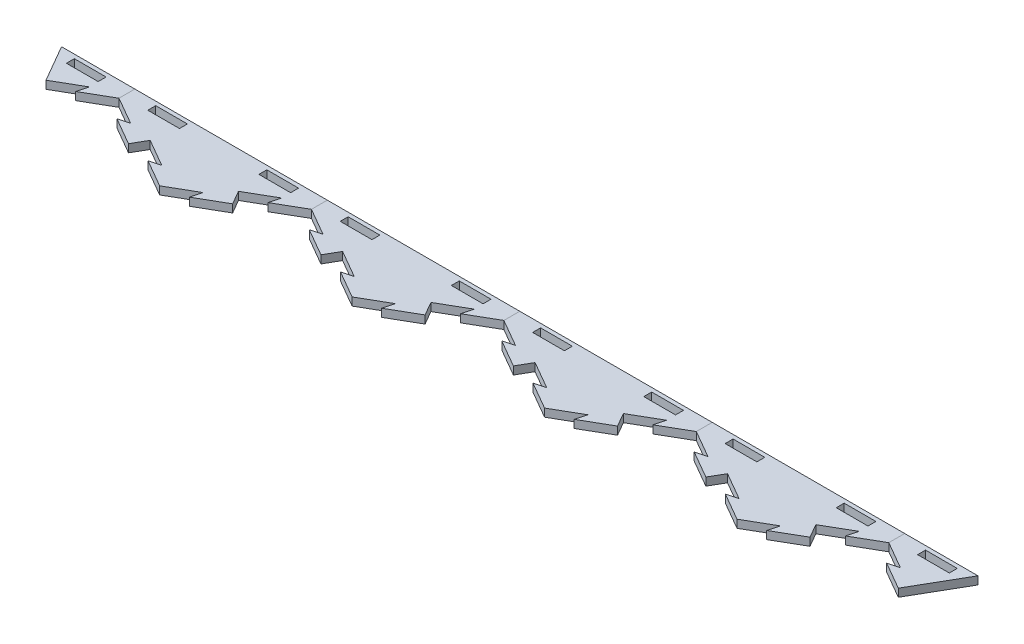
SolidWorks part; units mm, degrees
material "Cedar"
ref_plane "Front Plane" through (0, 0, 0) normal (0, 0, 1) x (1, 0, 0)
ref_plane "Top Plane" through (0, 0, 0) normal (0, 1, 0) x (1, 0, 0)
ref_plane "Right Plane" through (0, 0, 0) normal (1, 0, 0) x (0, 0, -1)
sketch "Sketch1" plane through (0, 0, 0) normal (0, 1, 0) x (1, 0, 0)
  line L0 (-76.9897, 0) -> (76.9897, 0) construction
  line L1 (-76.9897, 0) -> (0, -44.45)
  line L2 (0, -44.45) -> (76.9897, 0)
  line L3 (76.9897, 0) -> (76.9897, 88.9)
  line L4 (76.9897, 88.9) -> (0, 133.35)
  line L5 (0, 133.35) -> (-76.9897, 88.9)
  line L6 (-76.9897, 88.9) -> (-76.9897, 0)
  line L7 (0, -44.45) -> (0, 44.45) construction
  circle A0 centre (0, 44.45) radius 76.9897 construction
  point P1 (17.7378, -55.0895)
  point P9 (0, 0)
  dimension "D1" = 88.9
extrude "Boss-Extrude1" add sketch "Sketch1" against normal blind 6.35
sketch "Sketch2" plane through (0, 0, 0) normal (0, 1, 0) x (1, 0, 0)
  line L0 (-76.9897, 44.45) -> (76.9897, 44.45) construction
  line L1 (-76.9897, 88.9) -> (-76.9897, 0) construction
  line L2 (76.9897, 0) -> (76.9897, 88.9) construction
  point P2 (0, 44.45)
ref_axis "Axis1" through (0, 0, -44.45) along (0, 1, 0)
sketch "Sketch10" plane through (0, 0, 0) normal (0, 1, 0) x (1, 0, 0)
  line L0 (0, -44.45) -> (-21.997, -31.75) construction
  line L1 (-21.997, -31.75) -> (-13.3228, -29.4257)
  line L2 (-13.3228, -29.4257) -> (-35.3198, -16.7257)
  line L3 (-35.3198, -16.7257) -> (-38.4948, -22.225)
  line L4 (-21.997, -31.75) -> (-38.4948, -22.225)
  line L5 (-76.9897, 0) -> (0, -44.45) construction
  dimension "D1" = 45
  dimension "D2" = 6.35
extrude "Cut-Extrude4" cut sketch "Sketch10" against normal through all
sketch "Sketch11" plane through (0, 0, 0) normal (0, 1, 0) x (1, 0, 0)
  line L0 (-38.4948, -22.225) -> (-76.9897, 0) construction
  line L1 (-38.4948, -22.225) -> (-41.6698, -27.7243)
  line L2 (-41.6698, -27.7243) -> (-63.6669, -15.0243)
  line L3 (-63.6669, -15.0243) -> (-54.9926, -12.7)
  line L4 (-54.9926, -12.7) -> (-38.4948, -22.225)
  line L5 (-54.9926, -12.7) -> (-76.9897, 0) construction
  line L6 (-54.9926, -12.7) -> (-76.9897, 0) construction
  line L7 (-76.9897, 0) -> (-38.4948, -22.225) construction
  line L8 (-76.9897, 88.9) -> (-76.9897, 0) construction
  dimension "D1" = 45
  dimension "D2" = 6.35
extrude "Boss-Extrude4" add sketch "Sketch11" against normal blind 6.35
pattern_circular "CirPattern1" count 2 every 60 about axis through (0, 0, -44.45) along (0, 1, 0) of "Cut-Extrude4", "Boss-Extrude4"
sketch "Sketch12" plane through (0, 0, 0) normal (0, 1, 0) x (1, 0, 0)
  line L0 (-76.9897, 12.7) -> (76.9897, 12.7)
  line L1 (-76.9897, 88.9) -> (-76.9897, 0) construction
  line L2 (76.9897, 0) -> (76.9897, 88.9) construction
  line L3 (76.9897, 12.7) -> (76.9897, 133.35)
  line L4 (76.9897, 133.35) -> (-76.9897, 133.35)
  line L5 (-76.9897, 133.35) -> (-76.9897, 12.7)
  line L6 (0, 0) -> (0, 12.7) construction
  dimension "D1" = 12.7
extrude "Cut-Extrude5" cut sketch "Sketch12" against normal through all
sketch "Sketch13" plane through (0, 0, 0) normal (0, 1, 0) x (1, 0, 0)
  line L0 (0, 0) -> (0, 12.7) construction
  line L1 (-76.9897, 12.7) -> (76.9897, 12.7) construction
  line L2 (-44.45, 6.35) -> (44.45, 6.35) construction
  line L4 (-57.15, 9.525) -> (-31.75, 9.525)
  line L5 (-57.15, 9.525) -> (-57.15, 3.175)
  line L6 (-57.15, 3.175) -> (-31.75, 3.175)
  line L7 (-31.75, 9.525) -> (-31.75, 3.175)
  line L8 (-57.15, 9.525) -> (-31.75, 3.175) construction
  line L9 (-57.15, 3.175) -> (-31.75, 9.525) construction
  line L10 (31.75, 9.525) -> (57.15, 9.525)
  line L11 (31.75, 9.525) -> (31.75, 3.175)
  line L12 (31.75, 3.175) -> (57.15, 3.175)
  line L13 (57.15, 9.525) -> (57.15, 3.175)
  line L14 (31.75, 9.525) -> (57.15, 3.175) construction
  line L15 (31.75, 3.175) -> (57.15, 9.525) construction
  point P7 (0, 6.35)
  point P8 (0, 6.35)
  dimension "D1" = 6.35
  dimension "D2" = 25.4
  dimension "D3" = 6.35
  dimension "D4" = 25.4
  dimension "D5" = 88.9
extrude "Cut-Extrude6" cut sketch "Sketch13" against normal through all
pattern_linear "LPattern1" count 5 spacing 153.9793 along (1, 0, 0) count 2 spacing 153.9793 along (-1, 0, 0) pattern seed only yes of bodies 136 131
sketch "Sketch14" plane through (0, 0, 0) normal (0, 1, 0) x (1, 0, 0)
  line L0 (615.9173, -44.45) -> (615.9173, 12.7)
  line L1 (538.9276, 12.7) -> (692.9069, 12.7) construction
  line L2 (615.9173, 12.7) -> (692.9069, 12.7)
  line L3 (692.9069, 12.7) -> (692.9069, -44.45)
  line L4 (692.9069, -44.45) -> (615.9173, -44.45)
  line L5 (-153.9793, -44.45) -> (-153.9793, 12.7)
  line L6 (-230.969, 12.7) -> (-76.9897, 12.7) construction
  line L7 (-153.9793, 12.7) -> (-230.969, 12.7)
  line L8 (-230.969, 12.7) -> (-230.969, -44.45)
  line L9 (-230.969, -44.45) -> (-153.9793, -44.45)
  line L10 (580.5974, -16.7257) -> (597.5864, 12.7)
  line L11 (597.5864, 12.7) -> (615.9173, 12.7)
  line L12 (580.5974, -16.7257) -> (574.2474, -27.7243)
  line L13 (574.2474, -27.7243) -> (615.9173, -44.45)
  line L14 (-112.3095, -27.7243) -> (-135.6484, 12.7)
  line L15 (-135.6484, 12.7) -> (-153.9793, 12.7)
  line L16 (-112.3095, -27.7243) -> (-134.3065, -40.4243)
  line L17 (-134.3065, -40.4243) -> (-153.9793, -44.45)
  line L18 (-118.6595, -16.7257) -> (-112.3095, -27.7243) construction
  line M5 (673.0673, 9.525) -> (673.0673, 3.175)
  line M6 (673.0673, 3.175) -> (647.6673, 3.175)
  line M7 (647.6673, 3.175) -> (647.6673, 9.525)
  line M8 (647.6673, 9.525) -> (673.0673, 9.525)
  line M13 (692.9069, 12.7) -> (538.9276, 12.7)
  line M19 (580.5974, -16.7257) -> (602.5945, -29.4257)
  line M20 (602.5945, -29.4257) -> (593.9202, -31.75)
  line M21 (593.9202, -31.75) -> (615.9173, -44.45)
  line M22 (615.9173, -44.45) -> (637.9143, -31.75)
  line M23 (637.9143, -31.75) -> (635.5901, -40.4243)
  line M24 (635.5901, -40.4243) -> (657.5871, -27.7243)
  line M25 (657.5871, -27.7243) -> (651.2371, -16.7257)
  line M26 (651.2371, -16.7257) -> (673.2341, -4.0257)
  line M27 (673.2341, -4.0257) -> (670.9099, -12.7)
  line M28 (670.9099, -12.7) -> (692.9069, 0)
  line M29 (692.9069, 0) -> (692.9069, 12.7)
extrude "Cut-Extrude7" cut sketch "Sketch14" against normal through all contours L17 L16 L14 L15 L5 | L10 L0 M19 M20 M21 M13 | L0 M22 M23 M24 M25 M26 M27 M28 M29 M13 M8 M5 M6 M7 | L8 L9 L5 L7 region at (603.1355, 0, 12.4572) region at (644.4492, 0, 8.9256) region at (-192.4741, 0, 15.875) region at (-138.3884, 0, 16.3957)
